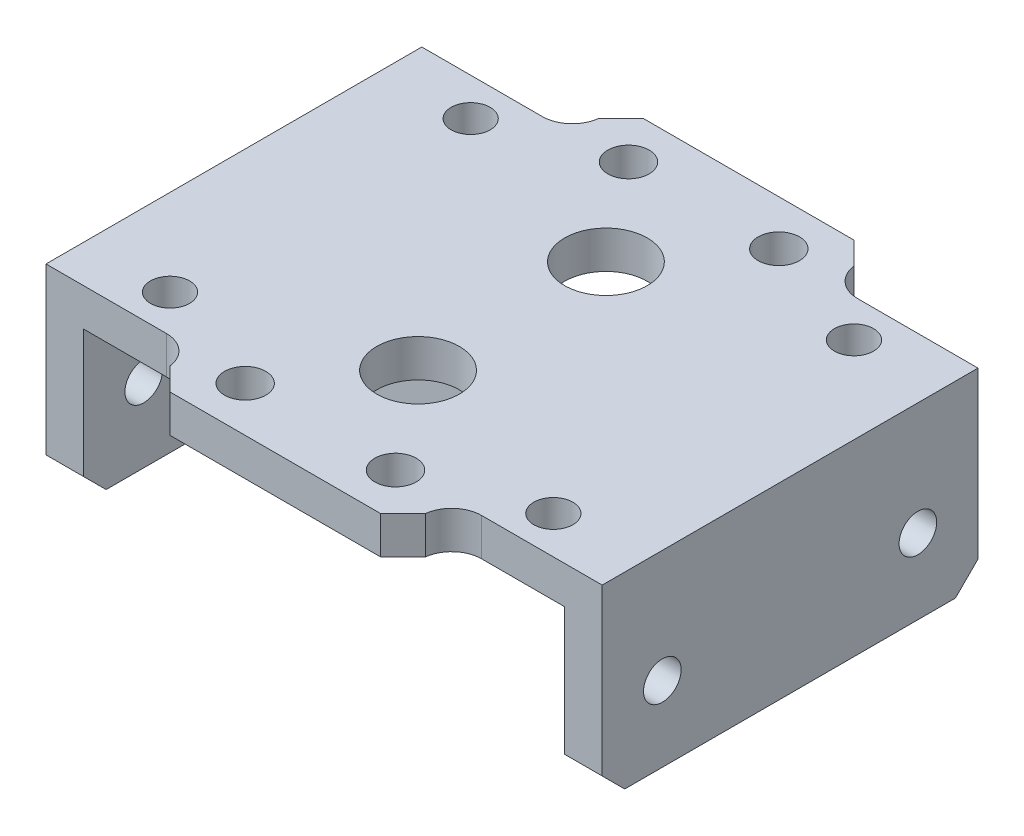
SolidWorks part; units mm, degrees
ref_plane "Front Plane" through (0, 0, 0) normal (0, 0, 1) x (1, 0, 0)
ref_plane "Top Plane" through (0, 0, 0) normal (0, 1, 0) x (1, 0, 0)
ref_plane "Right Plane" through (0, 0, 0) normal (1, 0, 0) x (0, 0, -1)
sketch "Sketch1" plane through (0, 0, 0) normal (0, 0, 1) x (1, 0, 0)
  line L0 (0, 0) -> (0, 25)
  line L1 (0, 25) -> (74, 25)
  line L2 (74, 25) -> (74, 0)
  line L3 (74, 0) -> (69, 0)
  line L4 (69, 0) -> (69, 20)
  line L5 (69, 20) -> (5, 20)
  line L6 (5, 20) -> (5, 0)
  line L7 (5, 0) -> (0, 0)
  point P6 (105.1497, 31.7365)
  dimension "D1" = 20
  dimension "D2" = 64
  dimension "D3" = 5
  dimension "D4" = 5
  dimension "D5" = 5
extrude "Boss-Extrude1" add sketch "Sketch1" along normal blind 50
sketch "Sketch2" plane through (5, 0, 0) normal (1, 0, 0) x (0, 0, -1)
  line L0 (-50, 10) -> (0, 10) construction
  line L1 (-50, 0) -> (-50, 20) construction
  line L2 (0, 0) -> (0, 20) construction
  circle A0 centre (-42, 10) radius 2.5
  circle A1 centre (-8, 10) radius 2.5
  dimension "D1" = 5
  dimension "D3" = 5
  dimension "D2" = 8
  dimension "D4" = 8
extrude "Cut-Extrude1" cut sketch "Sketch2" against normal mid plane 200
chamfer "Chamfer1" distance 3 angle 45 4 edges at (71.5, 0, 0) (71.5, 0, 50) (2.5, 0, 0) (2.5, 0, 50)
sketch "Sketch3" plane through (0, 25, 0) normal (0, 1, 0) x (1, 0, 0)
  circle A0 centre (11.5, -45) radius 2.6
  circle A1 centre (62.5, -45) radius 2.6
  circle A2 centre (62.5, -5) radius 2.6
  circle A3 centre (11.5, -5) radius 2.6
  dimension "D1" = 5.2
  dimension "D2" = 5.2
  dimension "D3" = 5.2
  dimension "D4" = 5.2
extrude "Cut-Extrude2" cut sketch "Sketch3" against normal through all
sketch "Sketch5" plane through (0, 20, 0) normal (0, -1, 0) x (1, 0, 0)
  circle A0 centre (11.5, 45) radius 5
  dimension "D1" = 10
sketch "Sketch6" plane through (0, 25, 0) normal (0, 1, 0) x (1, 0, 0)
  circle A0 centre (37, -37.5) radius 5.5
  circle A1 centre (37, -12.5) radius 5.5
  dimension "D1" = 11
  dimension "D2" = 11
extrude "Cut-Extrude3" cut sketch "Sketch6" against normal through all
sketch "Sketch7" plane through (0, 0, 0) normal (0, -1, 0) x (1, 0, 0)
  line L0 (0, 25) -> (74, 25) construction
  line L1 (0, 47) -> (0, 3) construction
  line L2 (74, 47) -> (74, 3) construction
  line L4 (0, 27.5) -> (74, 27.5)
  line L5 (0, 27.5) -> (0, 22.5)
  line L6 (0, 22.5) -> (74, 22.5)
  line L7 (74, 27.5) -> (74, 22.5)
  dimension "D1" = 2.5
  dimension "D2" = 2.5
extrude "Boss-Extrude2" add sketch "Sketch7" against normal up to surface (20 mm away) up to face at (31.5, 20, 37.5)
fillet "Fillet1" radius 4 4 edges at (69, 10, 27.5) (69, 10, 22.5) (5, 10, 22.5) (5, 10, 27.5)
sketch "Sketch8" plane through (0, 25, 0) normal (0, 1, 0) x (1, 0, 0)
  line L0 (37, 0) -> (37, 16.0917) construction
  line L1 (74, 0) -> (0, 0) construction
  line L3 (20, 6.5) -> (54, 6.5)
  line L4 (20, 6.5) -> (20, 0)
  line L5 (20, 0) -> (54, 0)
  line L6 (54, 6.5) -> (54, 0)
  dimension "D1" = 17
  dimension "D2" = 17
  dimension "D3" = 6.5
extrude "Boss-Extrude3" add sketch "Sketch8" against normal blind 5
ref_plane "Plane1" through (0, 0, 25) normal (0, 0, 1) x (1, 0, 0)
mirror "Mirror1" about plane through (0, 0, 25) normal (0, 0, 1) of "Boss-Extrude3"
sketch "Sketch9" plane through (0, 25, 0) normal (0, 1, 0) x (1, 0, 0)
  circle A0 centre (27, 0.5) radius 2.75
  circle A1 centre (47, 0.5) radius 2.75
  circle A2 centre (27, -50.5) radius 2.75
  circle A3 centre (47, -50.5) radius 2.75
  dimension "D1" = 5.5
  dimension "D2" = 5.5
  dimension "D3" = 5.5
  dimension "D4" = 5.5
extrude "Cut-Extrude4" cut sketch "Sketch9" against normal through all
chamfer "Chamfer2" distance 3 angle 45 4 edges at (54, 22.5, 56.5) (20, 22.5, 56.5) (54, 22.5, -6.5) (20, 22.5, -6.5)
fillet "Fillet2" radius 4 4 edges at (20, 22.5, 50) (54, 22.5, 50) (54, 22.5, 0) (20, 22.5, 0)
